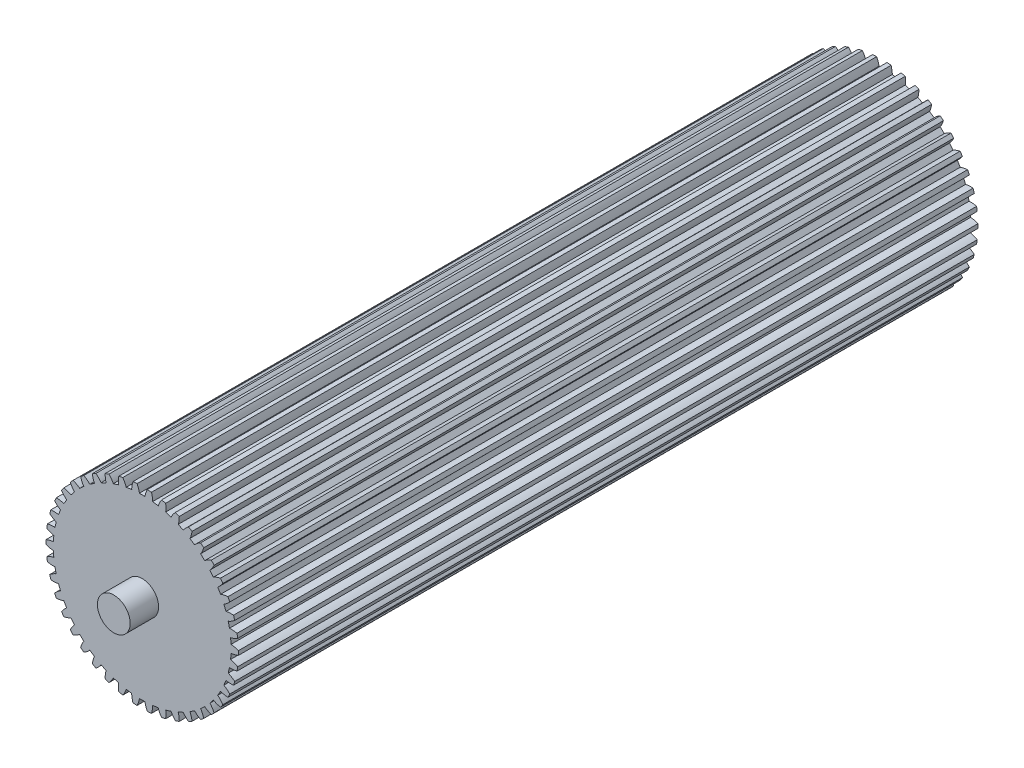
SolidWorks part; units mm, degrees
material "Brass"
ref_plane "Front Plane" through (0, 0, 0) normal (0, 0, 1) x (1, 0, 0)
ref_plane "Top Plane" through (0, 0, 0) normal (0, 1, 0) x (1, 0, 0)
ref_plane "Right Plane" through (0, 0, 0) normal (1, 0, 0) x (0, 0, -1)
sketch "Sketch1" plane through (0, 0, 0) normal (0, 0, 1) x (1, 0, 0)
  circle A0 centre (0, 0) radius 18.6267
  dimension "D1" = 37.2533
extrude "Boss-Extrude1" add sketch "Sketch1" along normal blind 143.2
sketch "Sketch2" plane through (0, 0, 0) normal (0, 0, 1) x (1, 0, 0)
  spline S0 degree 4 poles (17.1978, 0.739) (17.2039, 0.7392) (17.2154, 0.7393) (17.2343, 0.7391) (17.2715, 0.7379) (17.3137, 0.7353) (17.3614, 0.7312) (17.4127, 0.7257) (17.4566, 0.7203) (17.5005, 0.7141) (17.5443, 0.7075) (17.5973, 0.6986) (17.661, 0.6871) (17.7355, 0.6721) (17.8202, 0.6533) (17.9066, 0.6324) (17.9918, 0.6103) (18.078, 0.5862) (18.1615, 0.5616) (18.2484, 0.5343) (18.3286, 0.5082) (18.4188, 0.4769) (18.4915, 0.451) (18.5877, 0.4148) (18.6446, 0.3928) (18.7113, 0.3663) (18.7409, 0.3541) (18.7591, 0.3466) knots 0 0 0 0 0 0.015084 0.028532 0.04661 0.092111 0.119476 0.146842 0.174209 0.201575 0.228941 0.256307 0.307035 0.361767 0.4165 0.471232 0.525964 0.580697 0.635429 0.690161 0.744894 0.799626 0.854358 0.909091 0.954545 1 1 1 1 1 construction
  spline S1 degree 4 poles (17.1978, 0.739) (17.2039, 0.7392) (17.2154, 0.7393) (17.2343, 0.7391) (17.2715, 0.7379) (17.3137, 0.7353) (17.3614, 0.7312) (17.4127, 0.7257) (17.4566, 0.7203) (17.5005, 0.7141) (17.5443, 0.7075) (17.5973, 0.6986) (17.661, 0.6871) (17.7355, 0.6721) (17.8202, 0.6533) (17.9066, 0.6324) (17.9918, 0.6103) (18.078, 0.5862) (18.1615, 0.5616) (18.2484, 0.5343) (18.3286, 0.5082) (18.4188, 0.4769) (18.4915, 0.451) (18.5669, 0.4227) (18.6036, 0.4086) (18.6223, 0.4013) knots 0 0 0 0 0 0.015084 0.028532 0.04661 0.092111 0.119476 0.146842 0.174209 0.201575 0.228941 0.256307 0.307035 0.361767 0.4165 0.471232 0.525964 0.580697 0.635429 0.690161 0.744894 0.799626 0.854358 0.909091 0.909091 0.909091 0.909091 0.909091
  spline S2 degree 4 poles (17.1159, 1.8324) (17.1219, 1.8331) (17.1333, 1.8348) (17.152, 1.8378) (17.1886, 1.8446) (17.2299, 1.8534) (17.2765, 1.8645) (17.3264, 1.8776) (17.369, 1.8896) (17.4115, 1.9022) (17.4538, 1.9153) (17.5049, 1.9319) (17.5661, 1.9529) (17.6376, 1.9788) (17.7185, 2.0099) (17.8009, 2.0435) (17.8818, 2.0781) (17.9634, 2.1148) (18.0423, 2.1515) (18.1242, 2.1915) (18.1997, 2.2293) (18.2841, 2.2736) (18.3522, 2.31) (18.442, 2.3602) (18.4949, 2.3904) (18.5569, 2.4266) (18.5843, 2.4431) (18.6013, 2.4532) knots 0 0 0 0 0 0.015084 0.028532 0.04661 0.092111 0.119476 0.146842 0.174209 0.201575 0.228941 0.256307 0.307035 0.361767 0.4165 0.471232 0.525964 0.580697 0.635429 0.690161 0.744894 0.799626 0.854358 0.909091 0.954545 1 1 1 1 1 construction
  spline S3 degree 4 poles (17.1159, 1.8324) (17.1219, 1.8331) (17.1333, 1.8348) (17.152, 1.8378) (17.1886, 1.8446) (17.2299, 1.8534) (17.2765, 1.8645) (17.3264, 1.8776) (17.369, 1.8896) (17.4115, 1.9022) (17.4538, 1.9153) (17.5049, 1.9319) (17.5661, 1.9529) (17.6376, 1.9788) (17.7185, 2.0099) (17.8009, 2.0435) (17.8818, 2.0781) (17.9634, 2.1148) (18.0423, 2.1515) (18.1242, 2.1915) (18.1997, 2.2293) (18.2841, 2.2736) (18.3522, 2.31) (18.4225, 2.3493) (18.4567, 2.3687) (18.4742, 2.3787) knots 0 0 0 0 0 0.015084 0.028532 0.04661 0.092111 0.119476 0.146842 0.174209 0.201575 0.228941 0.256307 0.307035 0.361767 0.4165 0.471232 0.525964 0.580697 0.635429 0.690161 0.744894 0.799626 0.854358 0.909091 0.909091 0.909091 0.909091 0.909091
  spline S4 degree 1 poles (17.1159, 1.8324) (17.1978, 0.739) knots 0 0 1 1 construction
  spline S5 degree 1 poles (17.1159, 1.8324) (17.1978, 0.739) knots 0 0 1 1
  spline S6 degree 1 poles (18.6223, 0.4013) (59.9861, 1.2927) knots 0 0 1 1 construction
  spline S7 degree 1 poles (18.6223, 0.4013) (59.9861, 1.2927) knots 0 0 1 1
  spline S8 degree 4 poles (59.9965, 0.6495) (59.996, 0.6954) (59.9948, 0.7841) (59.9935, 0.9041) (59.9876, 1.2291) (59.9845, 1.3714) (59.9739, 1.7905) (59.9657, 2.0284) (59.9537, 2.3723) (59.9415, 2.6523) (59.9269, 2.9708) (59.9113, 3.2659) (59.8938, 3.5749) (59.875, 3.8756) (59.8545, 4.1808) (59.8325, 4.4838) (59.8091, 4.7868) (59.7838, 5.0915) (59.7577, 5.3917) (59.7289, 5.6999) (59.7003, 5.9941) (59.6673, 6.3111) (59.6376, 6.5899) (59.5983, 6.9317) (59.5709, 7.1681) (59.5189, 7.5842) (59.5007, 7.7253) (59.4582, 8.0476) (59.4416, 8.1664) (59.4295, 8.2543) (59.4232, 8.2997) knots 0 0 0 0 0 0.020959 0.041918 0.083333 0.123016 0.162698 0.202381 0.242063 0.281746 0.321429 0.361111 0.400794 0.440476 0.480159 0.519841 0.559524 0.599206 0.638889 0.678571 0.718254 0.757937 0.797619 0.837302 0.876984 0.916667 0.958082 0.979041 1 1 1 1 1 construction
  spline S9 degree 4 poles (59.9861, 1.2927) (59.9847, 1.3561) (59.9818, 1.4796) (59.9739, 1.7905) (59.9657, 2.0284) (59.9537, 2.3723) (59.9415, 2.6523) (59.9269, 2.9708) (59.9113, 3.2659) (59.8938, 3.5749) (59.875, 3.8756) (59.8545, 4.1808) (59.8325, 4.4838) (59.8091, 4.7868) (59.7838, 5.0915) (59.7577, 5.3917) (59.7289, 5.6999) (59.7003, 5.9941) (59.6673, 6.3111) (59.6376, 6.5899) (59.5983, 6.9317) (59.5709, 7.1681) (59.5324, 7.4768) (59.5168, 7.5993) (59.5087, 7.6622) knots 0.083333 0.083333 0.083333 0.083333 0.083333 0.123016 0.162698 0.202381 0.242063 0.281746 0.321429 0.361111 0.400794 0.440476 0.480159 0.519841 0.559524 0.599206 0.638889 0.678571 0.718254 0.757937 0.797619 0.837302 0.876984 0.916667 0.916667 0.916667 0.916667 0.916667
  spline S10 degree 1 poles (59.5087, 7.6622) (18.4742, 2.3787) knots 0 0 1 1 construction
  spline S11 degree 1 poles (59.5087, 7.6622) (18.4742, 2.3787) knots 0 0 1 1
extrude "Cut-Extrude2" cut sketch "Sketch2" against normal blind 144.2 and the other way blind 144.2
ref_axis "Axis1" through (0, 0, -15.835) along (0, 0, 1)
pattern_circular "CirPattern1" count 42 over 360 about axis through (0, 0, -15.835) along (0, 0, 1) of "Cut-Extrude2"
sketch "Sketch3" plane through (0, 0, 0) normal (0, 0, 1) x (1, 0, 0)
  circle A0 centre (0, 0) radius 3.175
  dimension "D1" = 6.35
extrude "Boss-Extrude2" add sketch "Sketch3" against normal blind 8 from offset 0 offset against normal yes
sketch "Sketch4" plane through (0, 0, 0) normal (0, 0, 1) x (1, 0, 0)
  circle A0 centre (0, 0) radius 3.175
  dimension "D1" = 6.35
extrude "Boss-Extrude3" add sketch "Sketch4" along normal blind 5.5 from offset 143.2
